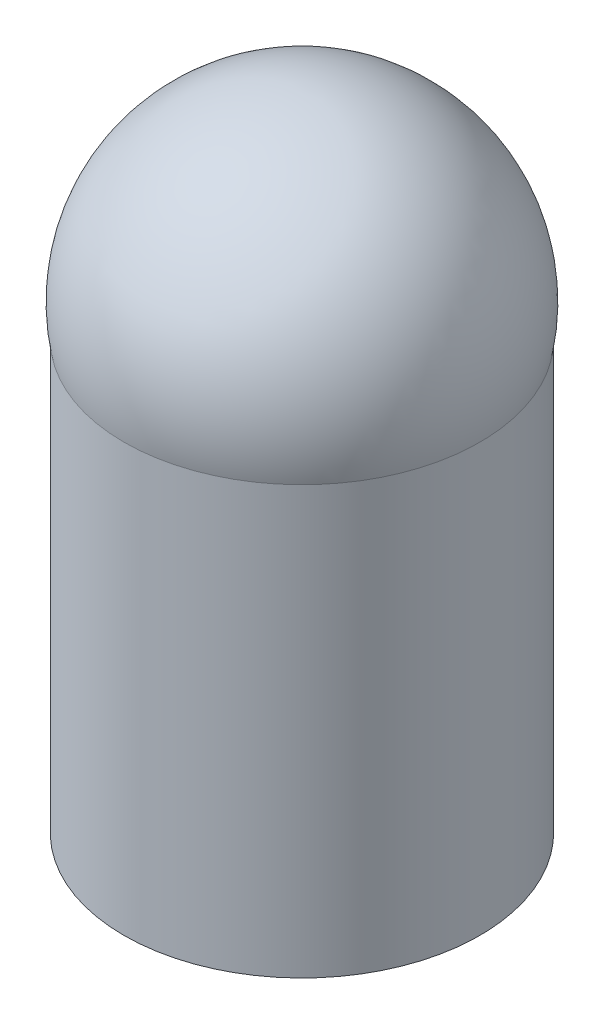
SolidWorks part; units mm, degrees
material "ABS PC"
ref_plane "Front Plane" through (0, 0, 0) normal (0, 0, 1) x (1, 0, 0)
ref_plane "Top Plane" through (0, 0, 0) normal (0, 1, 0) x (1, 0, 0)
ref_plane "Right Plane" through (0, 0, 0) normal (1, 0, 0) x (0, 0, -1)
sketch "Sketch1" plane through (0, 0, 0) normal (0, 1, 0) x (1, 0, 0)
  circle A0 centre (-23.3047, 11.2598) radius 2.5
  dimension "D1" = 5
extrude "Boss-Extrude1" add sketch "Sketch1" along normal blind 6
dome "Dome2" faces to dome 1 distance 3 reverse direction no elliptical dome no face at (-23.3047, 6, -8.7598) parameters "D1"=3
